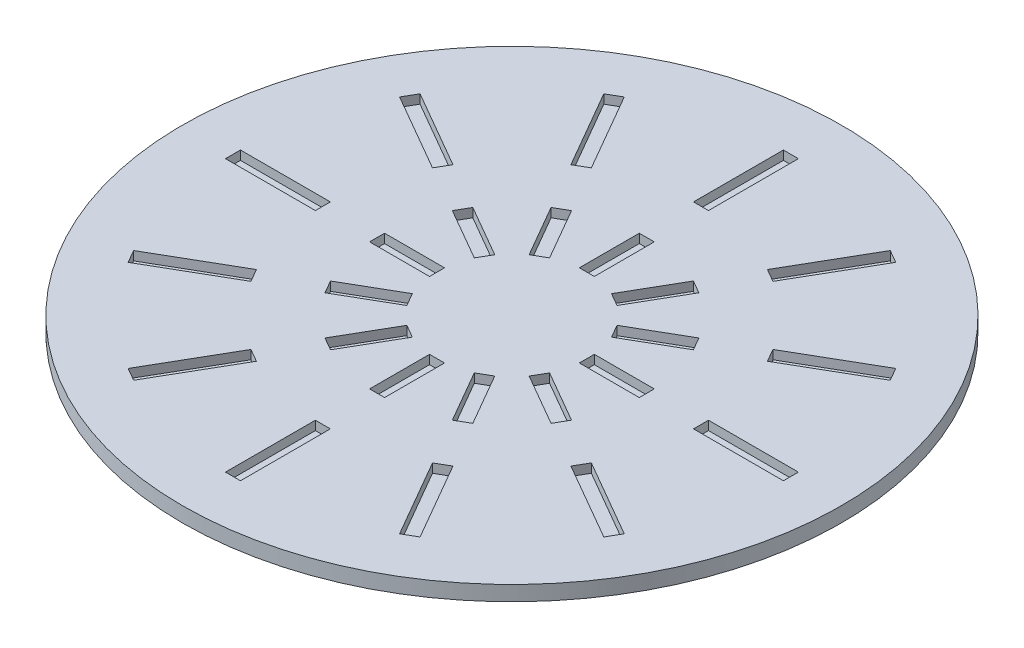
SolidWorks part; units mm, degrees
ref_plane "Front" through (0, 0, 0) normal (0, 0, 1) x (1, 0, 0)
ref_plane "Top" through (0, 0, 0) normal (0, 1, 0) x (1, 0, 0)
ref_plane "Right" through (0, 0, 0) normal (1, 0, 0) x (0, 0, -1)
ref_plane "Plane1" through (0, 0, 10) normal (0, 0, 1) x (1, 0, 0)
sketch "Sketch1" plane through (0, 0, 0) normal (0, 1, 0) x (1, 0, 0)
  line L0 (0, 0) -> (0, 109.9792) construction
  line L2 (-2.5, 63.0893) -> (2.5, 63.0893)
  line L3 (-2.5, 63.0893) -> (-2.5, 93.0893)
  line L4 (-2.5, 93.0893) -> (2.5, 93.0893)
  line L5 (2.5, 63.0893) -> (2.5, 93.0893)
  line L6 (-2.5, 63.0893) -> (2.5, 93.0893) construction
  line L7 (-2.5, 93.0893) -> (2.5, 63.0893) construction
  line L8 (-2.5, 25) -> (2.5, 25)
  line L9 (-2.5, 25) -> (-2.5, 45)
  line L10 (-2.5, 45) -> (2.5, 45)
  line L11 (2.5, 25) -> (2.5, 45)
  line L12 (-2.5, 25) -> (2.5, 45) construction
  line L13 (-2.5, 45) -> (2.5, 25) construction
  circle A0 centre (0, 0) radius 109.9792
  circle A1 centre (0, 0) radius 55.7895
  point P4 (0, 78.0893)
  point P10 (0, 35)
  dimension "D1" = 5
  dimension "D4" = 30
  dimension "D5" = 20
  dimension "D6" = 25
extrude "Boss-Extrude1" add sketch "Sketch1" against normal blind 5 contours A0 A1 L5 L2 L3 L4 | L3 L4 L5 L2 region at (-106.8685, 0, 0)
extrude "Boss-Extrude2" add sketch "Sketch1<3>" against normal blind 10 contours A1 L11 L8 L9 L10 | L11 L10 L9 L8 region at (0, 0, 0.3616)
sketch "Sketch1<3>" plane through (0, 0, 0) normal (0, 1, 0) x (1, 0, 0) same geometry as "Sketch1"
extrude "Cut-Extrude1" cut sketch "Sketch1<4>" against normal blind 3 contours L8 L11 L10 L9 | L2 L5 L4 L3 region at (0, 0, -78.0893) region at (0, 0, -35)
sketch "Sketch1<4>" plane through (0, 0, 0) normal (0, 1, 0) x (1, 0, 0) same geometry as "Sketch1"
sketch "Sketch3" plane through (0, 0, 0) normal (0, 0, 1) x (1, 0, 0)
  line L0 (0, 0) -> (0, 37.6313) construction
pattern_circular "CirPattern1" count 12 over 360 about axis through (0, 0, 0) along (0, 1, 0) of "Cut-Extrude1" reverse direction yes
sketch "Sketch4" plane through (0, 0, 10) normal (0, 0, 1) x (1, 0, 0)
  line L0 (0, 0) -> (0, 37.6313) construction
  line L1 (-30.0573, -10) -> (30.0573, -10)
  line L2 (-30.0573, -10.7742) -> (-30.0573, 0) construction
  line L3 (-30.0573, 0) -> (30.0573, 0) construction
  line L4 (30.0573, -10.7742) -> (30.0573, 0) construction
  line L5 (-30.0573, -10.7742) -> (30.0573, 0) construction
  line L6 (-30.0573, 0) -> (30.0573, -10.7742) construction
  line L7 (-55.7895, -10) -> (55.7895, -10) construction
  line L8 (-30.0573, -10) -> (-30.0573, -10.7742)
  line L9 (30.0573, -10) -> (30.0573, -10.7742)
  line L10 (0, 0) -> (0, -46.5299) construction
  arc A0 (-30.0573, -10.7742) -> (30.0573, -10.7742) centre (0, -16.0185) ccw
  circle A1 centre (0, -26.6252) radius 2.2616
  circle A3 centre (0, -26.6252) radius 2.2616 construction
  point P0 (0, -5.3871)
extrude "Boss-Extrude3" add sketch "Sketch4" along normal blind 8
mirror "Mirror1" about plane through (0, 0, 0) normal (0, 0, 1) of "Boss-Extrude3"
chamfer "Chamfer1" distance 5 angle 25 1 edges at (0, -10, 55.7895) first distance on face at (0, -10, 55.7895)
